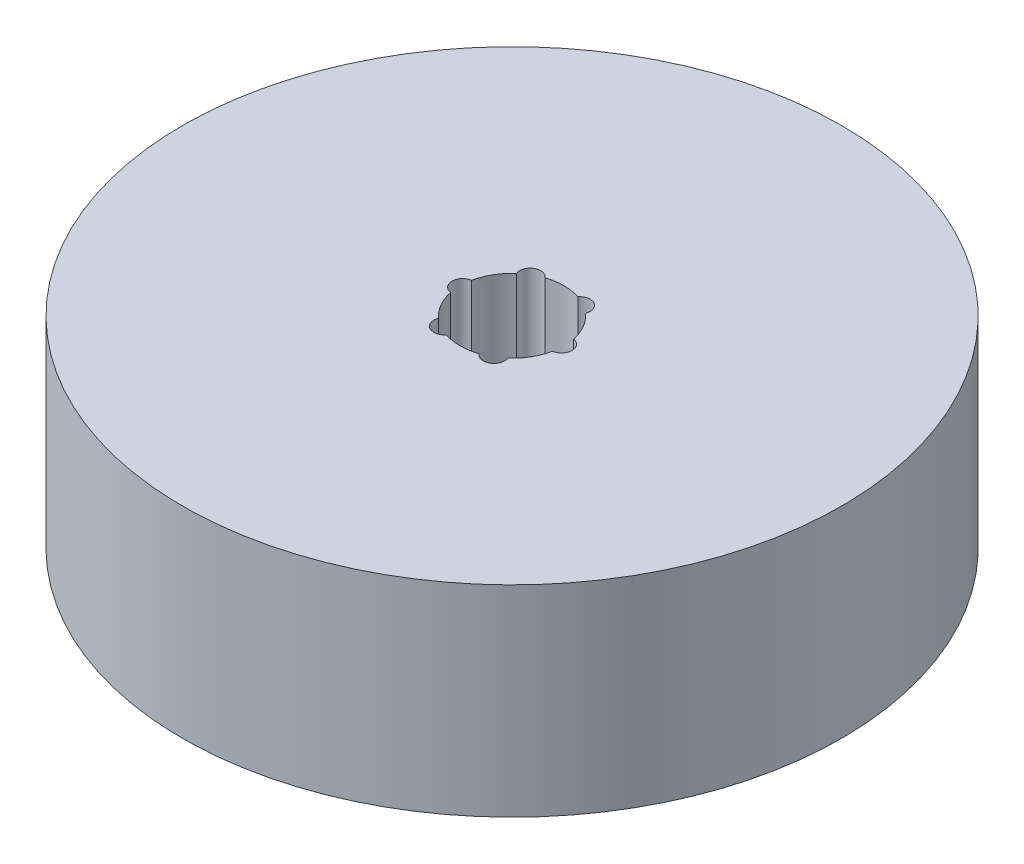
SolidWorks part; units mm, degrees
ref_plane "Front Plane" through (0, 0, 0) normal (0, 0, 1) x (1, 0, 0)
ref_plane "Top Plane" through (0, 0, 0) normal (0, 1, 0) x (1, 0, 0)
ref_plane "Right Plane" through (0, 0, 0) normal (1, 0, 0) x (0, 0, -1)
sketch "Sketch1" plane through (0, 0, 0) normal (0, 1, 0) x (1, 0, 0)
  circle A0 centre (0, 0) radius 47.5
  dimension "FLANGE_OD" = 95
extrude "Boss-Extrude1" add sketch "Sketch1" along normal blind 29
sketch "Sketch2" plane through (0, 0, 0) normal (0, 1, 0) x (1, 0, 0)
  circle A0 centre (0, 0) radius 7.5
  dimension "BORE_D" = 15
extrude "Cut-Extrude1" cut sketch "Sketch2" along normal through all
sketch "Sketch3" plane through (0, 29, 0) normal (0, 1, 0) x (1, 0, 0)
  circle A0 centre (0, 0) radius 7.1249 construction
  circle A1 centre (-7.1249, 0) radius 1.5335
  dimension "BOLT_D" = 3.0671
  dimension "BOLT_PCD" = 14.2498
extrude "Cut-Extrude2" cut sketch "Sketch3" against normal blind 26.5179
pattern_circular "CirPattern1" count 6 over 360 about axis through (0, 0, 0) along (0, 1, 0) of "Cut-Extrude2"
